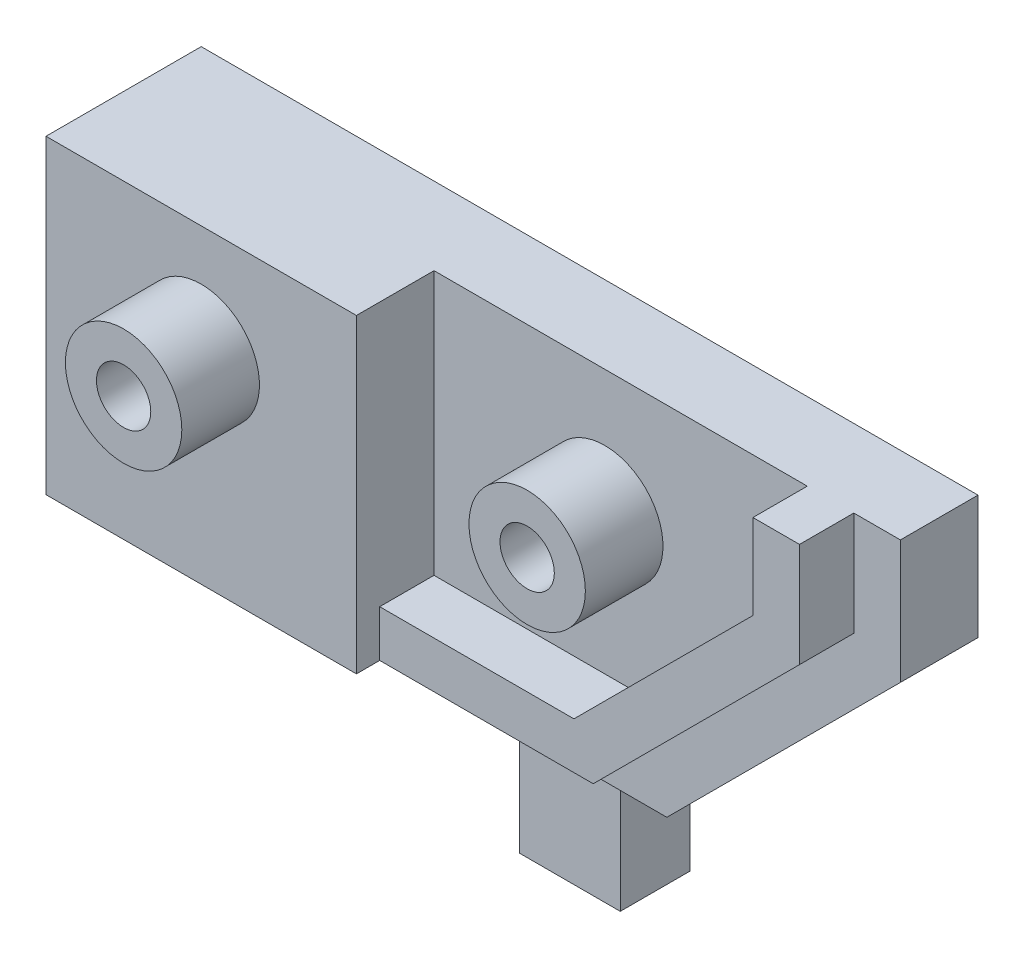
SolidWorks part; units mm, degrees
ref_plane "Front Plane" through (0, 0, 0) normal (0, 0, 1) x (1, 0, 0)
ref_plane "Top Plane" through (0, 0, 0) normal (0, 1, 0) x (1, 0, 0)
ref_plane "Right Plane" through (0, 0, 0) normal (1, 0, 0) x (0, 0, -1)
sketch "Sketch1" plane through (0, 0, 0) normal (0, 1, 0) x (1, 0, 0)
  line L10 (-18, -5.5617) -> (-18, -10) construction
  line L11 (0, 0) -> (-18, 0)
  line L12 (0, 0) -> (0, -5)
  line L13 (0, -5) -> (-15, -5)
  line L14 (-18, 0) -> (-18, -5.5617) construction
  line L16 (-15, -5) -> (-15, -10)
  line L17 (-15, -10) -> (-35, -10)
  line L18 (-35, -5) -> (-35, -10)
  line L19 (-18, 0) -> (-22, 0)
  line L21 (-35, -5) -> (-35, 0)
  line L22 (-35, 0) -> (-22, 0)
  dimension "D1" = 20
  dimension "D2" = 5
  dimension "D3" = 5
  dimension "D4" = 18
  dimension "D7" = 15
extrude "Boss-Extrude1" add sketch "Sketch1" along normal blind 23
sketch "Sketch2" plane through (0, 0, 10) normal (0, 0, 1) x (1, 0, 0)
  line L0 (-35, 23) -> (-35, 0) construction
  line L1 (-35, 0) -> (-15, 0) construction
  line L2 (-15, 0) -> (0, 0) construction
  line L3 (0, 23) -> (0, 0) construction
  circle A0 centre (-25, 16) radius 1.75
  circle A1 centre (-4, 15) radius 1.75
  dimension "D5" = 3.5
  dimension "D6" = 3.5
  dimension "D1" = 10
  dimension "D2" = 16
  dimension "D3" = 15
  dimension "D4" = 4
extrude "Cut-Extrude1" cut sketch "Sketch2" against normal through all
sketch "Sketch3" plane through (0, 0, 0) normal (0, -1, 0) x (1, 0, 0)
  line L0 (-25, 10) -> (-25, 0) construction
  line L1 (-35, 10) -> (-15, 10) construction
  line L3 (0, 0) -> (-35, 0) construction
  line L5 (0, 2.5) -> (-35, 2.5) construction
  line L6 (0, 5) -> (0, 0) construction
  line L7 (-35, 0) -> (-35, 10) construction
  circle A1 centre (-25, 2.5) radius 1.5
  dimension "D1" = 3
extrude "Cut-Extrude2" cut sketch "Sketch3" against normal blind 10
sketch "Sketch4" plane through (0, 0, 0) normal (0, -1, 0) x (1, 0, 0)
  line L0 (-35, 2.5) -> (0, 2.5) construction
  line L1 (-15, 5) -> (0, 5) construction
  line L2 (0, 5) -> (0, 0) construction
  line L3 (-35, 0) -> (-35, 10) construction
  line L7 (-9.75, 0.25) -> (-3.25, 0.25)
  line L8 (-9.75, 0.25) -> (-9.75, 4.75)
  line L9 (-9.75, 4.75) -> (-3.25, 4.75)
  line L10 (-3.25, 0.25) -> (-3.25, 4.75)
  line L11 (-9.75, 0.25) -> (-3.25, 4.75) construction
  line L12 (-9.75, 4.75) -> (-3.25, 0.25) construction
  point P12 (-6.5, 2.5)
  dimension "D1" = 6.5
  dimension "D2" = 0.25
  dimension "D3" = 3.25
extrude "Boss-Extrude2" add sketch "Sketch4" along normal blind 7
sketch "Sketch5" plane through (0, 0, 10) normal (0, 0, 1) x (1, 0, 0)
  circle A0 centre (-25, 16) radius 1.75
  circle A1 centre (-25, 16) radius 3.75
  circle A2 centre (-25, 16) radius 1.75 construction
  dimension "D1" = 2
extrude "Boss-Extrude3" add sketch "Sketch5" along normal blind 5
sketch "Sketch6" plane through (0, 0, 5) normal (0, 0, 1) x (1, 0, 0)
  circle A0 centre (-4, 15) radius 1.75
  circle A1 centre (-4, 15) radius 1.75 construction
  circle A2 centre (-4, 15) radius 3.75
  dimension "D1" = 2
extrude "Boss-Extrude4" add sketch "Sketch6" along normal blind 5
sketch "Sketch7" plane through (0, 0, 5) normal (0, 0, 1) x (1, 0, 0)
  line L0 (0, 0) -> (0, 23)
  line L1 (0, 23) -> (15.0472, 23)
  line L2 (15.0472, 15.0472) -> (0, 0)
  line L3 (15.0472, 23) -> (15.0472, 15.0472)
  dimension "D1" = 45
  dimension "D2" = 21.28
extrude "Boss-Extrude5" add sketch "Sketch7" against normal blind 5
sketch "Sketch8" plane through (0, 0, 5) normal (0, 0, 1) x (1, 0, 0)
  line L0 (12.0472, 23) -> (12.0472, 16.2899)
  line L1 (-15, 23) -> (15.0472, 23) construction
  line L2 (12.0472, 16.2899) -> (-1.2426, 3)
  line L3 (-1.2426, 3) -> (-15, 3)
  line L4 (-15, 23) -> (-15, 0) construction
  line L5 (15.0472, 15.0472) -> (15.0472, 23) construction
  line L6 (0, 0) -> (15.0472, 15.0472) construction
  line L7 (-15, 0) -> (0, 0) construction
  line L8 (9.0472, 23) -> (9.0472, 17.5325)
  line L9 (9.0472, 17.5325) -> (-2.4853, 6)
  line L10 (-2.4853, 6) -> (-15, 6)
  line L11 (9.0472, 23) -> (12.0472, 23)
  line L12 (-15, 6) -> (-15, 3)
  dimension "D1" = 3
  dimension "D2" = 3
  dimension "D3" = 3
  dimension "D4" = 3
extrude "Boss-Extrude6" add sketch "Sketch8" along normal blind 3.5
sketch "Sketch9" plane through (-15, 0, 0) normal (1, 0, 0) x (0, 0, -1)
  line L1 (-5, 3) -> (-10, 3)
  line L2 (-5, 3) -> (-5, 0)
  line L3 (-5, 0) -> (-10, 0)
  line L4 (-10, 3) -> (-10, 0)
extrude "Cut-Extrude3" cut sketch "Sketch9" against normal up to surface (20 mm away) contours L2 L1 L4 L3 up to face at (-35, 11.5, 5)
sketch "Sketch10" plane through (0, 0, 0) normal (0, 0, -1) x (-1, 0, 0)
  circle A0 centre (4, 15) radius 2.5
  circle A1 centre (25, 16) radius 2.5
  dimension "D1" = 5
  dimension "D2" = 5
extrude "Cut-Extrude4" cut sketch "Sketch10" against normal blind 4
